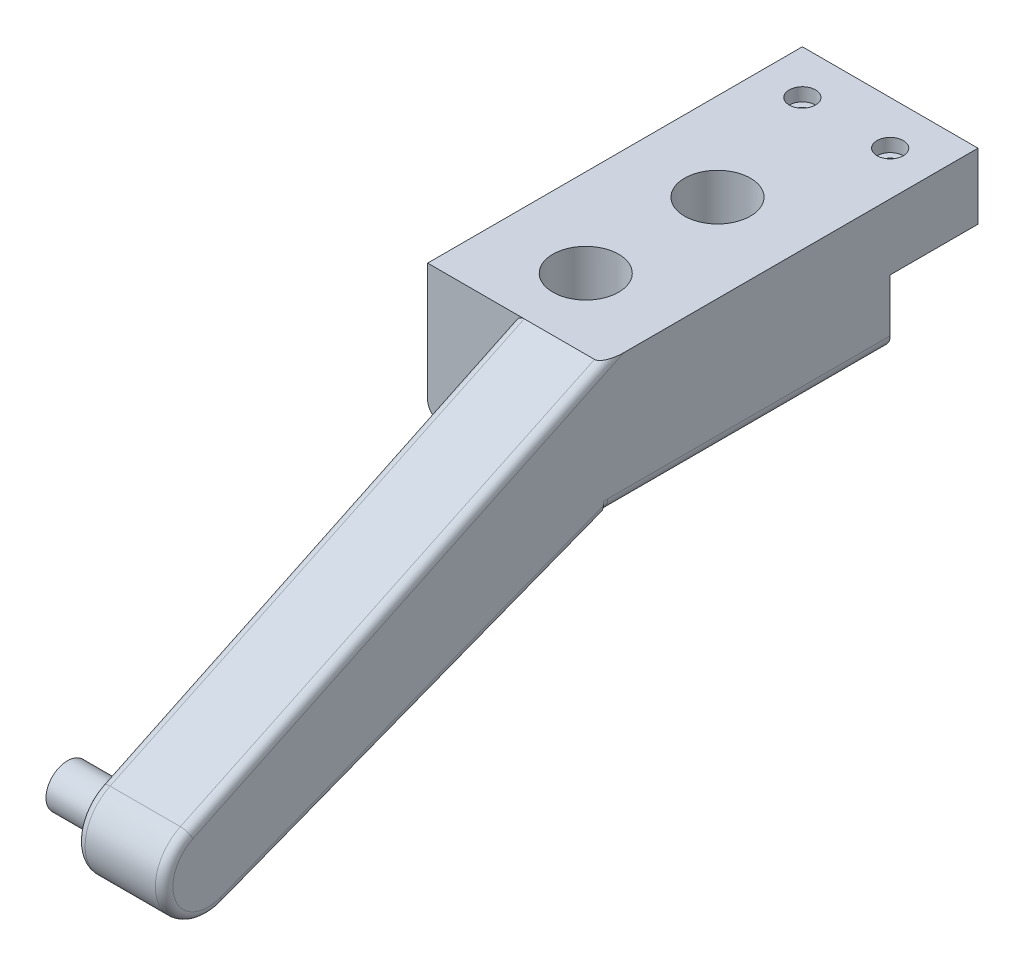
SolidWorks part; units mm, degrees
ref_plane "Front Plane" through (0, 0, 0) normal (0, 0, 1) x (1, 0, 0)
ref_plane "Top Plane" through (0, 0, 0) normal (0, 1, 0) x (1, 0, 0)
ref_plane "Right Plane" through (0, 0, 0) normal (1, 0, 0) x (0, 0, -1)
sketch "Sketch1" plane through (0, 0, 0) normal (0, 1, 0) x (1, 0, 0)
  line L1 (-20, 75) -> (20, 75)
  line L3 (-20, -75) -> (20, -75)
  line L4 (20, -75) -> (20, 75)
  line L5 (-20, -75) -> (-20, 75)
  circle A0 centre (0, -61.1649) radius 7.5
  circle A1 centre (0, -31.1649) radius 7.5
extrude "Boss-Extrude1" add sketch "Sketch1" against normal blind 30 contours L5 L1 L4 L3
sketch "Sketch3" plane through (0, 0, 0) normal (0, 1, 0) x (1, 0, 0)
  circle A0 centre (0, -60) radius 7.5
  circle A1 centre (0, -30) radius 7.5
extrude "Cut-Extrude1" cut sketch "Sketch3" against normal blind 30 contours A0 | A1
sketch "Sketch4" plane through (-20, 0, 0) normal (-1, 0, 0) x (0, 0, 1)
  line L1 (-75, -30) -> (-75, 0) construction
  line L2 (-75, -8) -> (0, -30)
  line L3 (75, -30) -> (-75, -30) construction
  line L4 (0, -30) -> (-75, -30)
  line L5 (-75, -30) -> (-75, -8)
extrude "Cut-Extrude2" cut sketch "Sketch4" against normal blind 49
sketch "Sketch6" plane through (0, 0, -75) normal (0, 0, -1) x (-1, 0, 0)
  line L1 (-20, 0) -> (20, 0)
  line L2 (-20, 0) -> (-20, -30)
  line L3 (-20, -30) -> (20, -30)
  line L4 (20, 0) -> (20, -30)
extrude "Boss-Extrude2" add sketch "Sketch6" along normal blind 50 and the other way blind 87
sketch "Sketch7" plane through (-20, 0, 0) normal (-1, 0, 0) x (0, 0, 1)
  line L1 (-125, -30) -> (-125, 0) construction
  line L2 (-125, -10) -> (-25, -30)
  line L3 (75, -30) -> (-125, -30) construction
  line L4 (-25, -30) -> (-125, -30)
  line L5 (-125, -30) -> (-125, -10)
extrude "Cut-Extrude3" cut sketch "Sketch7" against normal blind 50
sketch "Sketch8" plane through (0, 0, 75) normal (0, 0, 1) x (1, 0, 0)
  line L10 (20, -30) -> (6, -30)
  line L11 (-20, -30) -> (20, -30) construction
  line L12 (6, -30) -> (6, 0)
  line L13 (-20, 0) -> (20, 0) construction
  line L14 (6, 0) -> (20, 0)
  line L15 (20, 0) -> (20, -30)
  line L16 (-20, -30) -> (-6, -30)
  line L17 (-6, -30) -> (-6, 0)
  line L18 (-6, 0) -> (-20, 0)
  line L19 (-20, -30) -> (-20, 0) construction
  line L20 (-20, 0) -> (-20, -30)
extrude "Boss-Extrude4" add sketch "Sketch8" along normal blind 50
sketch "Sketch11" plane through (0, 0, 0) normal (0, 1, 0) x (1, 0, 0)
  line L0 (6, -75) -> (20, -75)
  line L1 (20, -125) -> (20, 125) construction
  line L2 (20, -75) -> (20, -125)
  line L3 (20, -125) -> (6, -125)
  line L4 (6, -125) -> (6, -75)
  line L5 (-6, -75) -> (-6, -125)
  line L6 (-6, -125) -> (-20, -125)
  line L7 (-20, -125) -> (-20, -75)
  line L8 (-20, -125) -> (-20, 125) construction
  line L9 (-20, -75) -> (-6, -75)
extrude "Cut-Extrude4" cut sketch "Sketch11" against normal blind 15
sketch "Sketch12" plane through (0, 0, 125) normal (0, 0, 1) x (1, 0, 0)
  line L1 (-20, -15) -> (-6, -15)
  line L2 (-20, -15) -> (-20, -30)
  line L3 (-20, -30) -> (-6, -30)
  line L4 (-6, -15) -> (-6, -30)
  line L5 (6, -15) -> (20, -15)
  line L6 (6, -15) -> (6, -30)
  line L7 (6, -30) -> (20, -30)
  line L8 (20, -15) -> (20, -30)
extrude "Boss-Extrude5" add sketch "Sketch12" along normal blind 10
sketch "Sketch13" plane through (-6, 0, 0) normal (1, 0, 0) x (0, 0, -1)
  circle A0 centre (-125, -22.5) radius 5
extrude "Boss-Extrude6" add sketch "Sketch13" along normal up to surface (12 mm away) contours A0 up to face at (6, -22.5, 105)
sketch "Sketch14" plane through (0, -30, 0) normal (0, -1, 0) x (1, 0, 0)
  circle A0 centre (0, 60) radius 7.5
  circle A1 centre (0, 60) radius 6
  circle A2 centre (0, 30) radius 6
  circle A3 centre (0, 30) radius 7.5
extrude "Boss-Extrude7" add sketch "Sketch14" against normal blind 5
sketch "Sketch15" plane through (20, 0, 0) normal (1, 0, 0) x (0, 0, -1)
  line L0 (125, 0) -> (105, 0)
  line L1 (-75, 0) -> (125, 0) construction
  circle A0 centre (52.5, 373.9316) radius 377.5991
extrude "Cut-Extrude5" cut sketch "Sketch15" against normal blind 50 contours A0
fillet "Fillet1" radius 3 2 edges at (20, -30, 55) (-20, -30, 55)
fillet "Fillet2" radius 3 8 edges at (-20, -18.5, -82.5) (-19.1213, -29.1213, -29.3934) (0, -30, -25) (19.1213, -29.1213, -29.3934) (-20, -5, -125) (20, -5, -125) (0, -10, -125) (20, -18.5, -82.5)
sketch "Sketch17" plane through (0, 0, 75) normal (0, 0, 1) x (1, 0, 0)
  line L0 (20, 0) -> (20, -30)
  line L1 (14.0365, -30) -> (20, -30)
  line L2 (6, -30) -> (17, -30) construction
  line L3 (20, 0) -> (-20, 0)
  line L4 (-20, 0) -> (-20, -30)
  line L5 (-20, -30) -> (14.0365, -30)
extrude "Boss-Extrude11" add sketch "Sketch17" along normal up to surface (60 mm away) up to face at (13.9243, -23.5243, 135)
sketch "Sketch23" plane through (0, 0, 135) normal (0, 0, 1) x (1, 0, 0)
  line L0 (-20, -15) -> (0, -15)
  line L1 (-20, 0) -> (-20, -30) construction
  line L3 (0, -30) -> (0, -15)
  line L4 (-20, -30) -> (20, -30) construction
  line L6 (-20, -30) -> (0, -30)
  line L7 (-20, -15) -> (-20, -30)
  line L9 (-20, -30) -> (20, -30)
  line L10 (-20, -30) -> (-20, 0)
  line L11 (-20, 0) -> (20, 0)
  line L12 (20, -30) -> (20, 0)
  line M1 (-20, 0) -> (-20, -30)
  line M2 (-20, -30) -> (20, -30)
  line M3 (20, -30) -> (20, 0)
  line M4 (20, 0) -> (-20, 0)
extrude "Cut-Extrude8" cut sketch "Sketch23" against normal up to surface (60 mm away) contours L3 L0 M2 M3 M4 M1 region at (3.3333, -12.5, 135) up to face at (19.2071, -29.2071, 75)
sketch "Sketch25" plane through (0, 0, 75) normal (0, 0, 1) x (1, 0, 0)
  line L0 (-20, -15) -> (-20, 0)
  line L1 (-20, 0) -> (0, 0)
  line L2 (-20, 0) -> (20, 0) construction
  line L3 (0, 0) -> (0, -15)
  line L4 (0, -15) -> (-20, -15)
extrude "Boss-Extrude13" add sketch "Sketch25" along normal up to surface (60 mm away) up to face at (-10, -22.5, 135)
sketch "Sketch26" plane through (0, 0, 0) normal (1, 0, 0) x (0, 0, -1)
  circle A0 centre (-125, -15) radius 5
extrude "Boss-Extrude14" add sketch "Sketch26" along normal up to surface (20 mm away) up to face at (20, -9.3154, -31.9576)
sketch "Sketch27" plane through (0, 0, 75) normal (0, 0, 1) x (1, 0, 0)
  line L1 (20, 0) -> (-20, 0)
  line L2 (20, 0) -> (20, -60)
  line L3 (20, -60) -> (-20, -60)
  line L4 (-20, 0) -> (-20, -60)
extrude "Boss-Extrude15" add sketch "Sketch27" along normal up to surface (60 mm away) up to face at (-10, -15, 135)
sketch "Sketch28" plane through (0, 0, 75) normal (0, 0, -1) x (-1, 0, 0)
  line L0 (20, -27) -> (20, -60) construction
  line L1 (-20, -60) -> (20, -60)
  line L2 (-20, -60) -> (-20, -30)
  line L3 (-20, -30) -> (20, -30)
  line L4 (20, -60) -> (20, -30)
extrude "Cut-Extrude9" cut sketch "Sketch28" against normal blind 1
sketch "Sketch29" plane through (0, 0, 135) normal (0, 0, 1) x (1, 0, 0)
  line L0 (20, 0) -> (-20, 0) construction
  line L1 (20, -60) -> (0, -60)
  line L2 (20, -60) -> (20, 0)
  line L3 (20, 0) -> (0, 0)
  line L4 (0, -60) -> (0, 0)
extrude "Cut-Extrude10" cut sketch "Sketch29" against normal up to surface (59 mm away) up to face at (0, -45, 76)
fillet "Fillet6" radius 3 1 edges at (-20, -30, 75.5)
fillet "Fillet7" radius 3 1 edges at (20, -30, 75.5)
sketch "Sketch30" plane through (0, 0, 135) normal (0, 0, 1) x (1, 0, 0)
  line L0 (-20, 0) -> (-20, -30)
  line L1 (-20, 0) -> (-20, -60) construction
  line L2 (-20, -15) -> (0, -15)
  line L3 (0, 0) -> (0, -60) construction
  line L4 (0, -15) -> (0, 0)
  line L5 (0, 0) -> (-20, 0)
  line M1 (0, -60) -> (0, 0)
  line M2 (0, 0) -> (-20, 0)
  line M3 (-20, 0) -> (-20, -60)
extrude "Cut-Extrude11" cut sketch "Sketch30" against normal up to surface (59 mm away) contours L2 M3 M1 M2 region at (-10, -7.5, 135) up to face at (11.5243, -17.5243, 76)
sketch "Sketch31" plane through (0, 0, 0) normal (1, 0, 0) x (0, 0, -1)
  line L0 (-129.7694, -41.2162) -> (-129.0122, -40.847)
  line L1 (-76, -15) -> (-76, -30)
  line L2 (-76, -30) -> (-118.7075, -57.7744)
  line L3 (-129.6113, -41.0081) -> (-129.7694, -41.2162)
  line L4 (-89.6197, -15) -> (-129.6113, -41.0081)
  line L5 (-76, -30) -> (-76, -60)
  line L6 (-76, -60) -> (-135, -60)
  line L7 (-135, -60) -> (-135, -15)
  line L8 (-135, -15) -> (-76, -15)
  line L9 (-96, -19.1494) -> (-129.6113, -41.0081) construction
  line L10 (-96, -15) -> (-96, -19.1494) construction
  circle A0 centre (-125.0122, -50.0122) radius 10
  line M9 (-76, -15) -> (-135, -15)
  line M10 (-135, -15) -> (-135, -60)
  line M11 (-135, -60) -> (-76, -60)
  line M12 (-76, -60) -> (-76, -30)
  dimension "D1" = 20
extrude "Cut-Extrude13" cut sketch "Sketch31" against normal blind 28 contours A0 M10 M11 | A0 L2 M11 M12 | A0 L3 L4 M9 M10 region at (0, -24.9817, 119.9741) region at (0, -57.7806, 132.7806) region at (0, -50.0084, 91.4032)
sketch "Sketch32" plane through (0, 0, 0) normal (1, 0, 0) x (0, 0, -1)
  line L0 (-76, -30) -> (-76, 0)
  line L1 (-76, 0) -> (-129.7694, -41.2162)
  line L2 (-129.7694, -41.2162) -> (-76, -30)
extrude "Boss-Extrude16" add sketch "Sketch32" against normal up to surface (20 mm away) up to face at (-20, -28.5466, 55.3206)
sketch "Sketch33" plane through (0, 0, 0) normal (1, 0, 0) x (0, 0, -1)
  circle A0 centre (-125.0122, -50.0122) radius 5
extrude "Boss-Extrude17" add sketch "Sketch33" along normal up to surface (20 mm away) contours A0 up to face at (20, -11.526, -18.3379)
ref_plane "Plane2" through (0, 10, 0) normal (0, 1, 0) x (1, 0, 0)
sketch "Sketch34" plane through (0, 0, 0) normal (1, 0, 0) x (0, 0, -1)
  line L0 (-129.6113, -41.0081) -> (-129.7694, -41.2162)
  line L1 (-129.6113, -41.0081) -> (-76, 0)
  line L2 (-76, 0) -> (-76, -30)
  line L3 (-76, -30) -> (-76, 0) construction
  line L4 (-76, -30) -> (-118.7075, -57.7744)
  arc A0 (-129.7694, -41.2162) -> (-118.7075, -57.7744) centre (-125.0122, -50.0122) ccw
extrude "Cut-Extrude15" cut sketch "Sketch34" against normal up to surface (20 mm away) up to face at (-20, -30.8448, 56.4126)
extrude "Cut-Extrude16" cut sketch "Sketch34<2>" along normal up to surface (20 mm away) up to face at (20, -11.526, -18.3379)
sketch "Sketch34<2>" plane through (0, 0, 0) normal (1, 0, 0) x (0, 0, -1) same geometry as "Sketch34"
extrude "Boss-Extrude19" add sketch "Sketch34<3>" along normal up to surface (20 mm away) up to face at (20, -11.526, -18.3379)
sketch "Sketch34<3>" plane through (0, 0, 0) normal (1, 0, 0) x (0, 0, -1) same geometry as "Sketch34"
sketch "Sketch38" plane through (0, 0, 0) normal (-1, 0, 0) x (0, 0, 1)
  circle A0 centre (125.0122, -50.0122) radius 5
sketch "Sketch39" plane through (0, 0, 0) normal (-1, 0, 0) x (0, 0, 1)
  line L0 (162.0273, -59.1835) -> (76, -78.9424)
  line L1 (169.997, -40.8408) -> (76, 0)
  line L2 (76, -30) -> (76, 0) construction
  line L3 (76, 0) -> (129.6113, -41.0081) construction
  line L4 (76, 0) -> (76, -30)
  line L6 (162.0273, -59.1835) -> (76, -30)
  line L7 (76, -78.9424) -> (76, -30)
  arc A0 (162.0273, -59.1835) -> (169.997, -40.8408) centre (166.0122, -50.0122) ccw
  line M6 (129.6113, -41.0081) -> (76, 0)
  line M8 (76, -30) -> (118.7075, -57.7744)
  arc M9 (118.7075, -57.7744) -> (129.7694, -41.2162) centre (125.0122, -50.0122) ccw
  line M10 (129.7694, -41.2162) -> (129.6113, -41.0081)
extrude "Cut-Extrude17" cut sketch "Sketch39" against normal blind 23 contours L7 L0 L6 M9 M8 | L6 M9 M8 region at (0, -58.461, 102.3812) region at (0, -47.5284, 112.7515)
extrude "Boss-Extrude21" add sketch "Sketch39<3>" against normal blind 20 contours L6 A0 L1 M6 M10 M9 region at (0, -36.3816, 138.4753)
sketch "Sketch39<3>" plane through (0, 0, 0) normal (-1, 0, 0) x (0, 0, 1) same geometry as "Sketch39"
sketch "Sketch40" plane through (0, -4.0074, 0) normal (-1, 0, 0) x (0, 0, 1)
  circle A0 centre (166.0122, -50.0122) radius 4.5
extrude "Boss-Extrude22" add sketch "Sketch40" along normal up to surface (12 mm away)
ref_plane "Plane5" through (0, 0, 0) normal (-1, 0, 0) x (0, 0, 1)
sketch "Sketch42" plane through (0, 0, 0) normal (-1, 0, 0) x (0, 0, 1)
  line L0 (166.0122, -54.0196) -> (166.0122, -54.0122)
  line L1 (170.3172, -44.9863) -> (76, 0)
  line L2 (76, 0) -> (76, -30)
  line L3 (162.4124, -63.3418) -> (76, -30)
  line L4 (175.8593, -55.7544) -> (179.2704, -36.4741)
  line L5 (179.2704, -36.4741) -> (76, 0)
  circle A0 centre (166.0122, -54.0122) radius 10
extrude "Cut-Extrude18" cut sketch "Sketch42" against normal blind 20 contours A0 L4 L5 L1 region at (0, -28.5967, 144.6768)
extrude "Boss-Extrude23" add sketch "Sketch42<4>" against normal blind 20 contours A0 L1 L2 L3 | A0 region at (0, -31.8969, 115.5317) region at (0, -48.8269, 174.2302)
sketch "Sketch42<4>" plane through (0, 0, 0) normal (-1, 0, 0) x (0, 0, 1) same geometry as "Sketch42"
sketch "Sketch43" plane through (0, 0, 0) normal (-1, 0, 0) x (0, 0, 1)
  circle A0 centre (166.0122, -54.0196) radius 5.5
extrude "Boss-Extrude24" add sketch "Sketch43" along normal blind 2
fillet "Fillet8" radius 2 6 edges at (20, -46.6709, 119.2062) (20, -57.9675, 175.1967) (0, -46.6709, 119.2062) (0, -57.9675, 175.1967) (20, -22.4932, 123.1586) (0, -22.4932, 123.1586)
sketch "Sketch44" plane through (20, 0, 0) normal (1, 0, 0) x (0, 0, -1)
  line L0 (0, 0) -> (105, 0)
  line L1 (105, 0) -> (105, -4.5055)
  line L2 (105, -4.5055) -> (0, -4.5055)
  line L3 (0, -4.5055) -> (0, 0)
extrude "Boss-Extrude25" add sketch "Sketch44" against normal up to surface (40 mm away) up to face at (-20, -11.526, -18.3379)
sketch "Sketch46" plane through (20, 0, 0) normal (1, 0, 0) x (0, 0, -1)
  line L0 (-71.3543, 0) -> (122, 0) construction
  line L1 (25.3229, 0) -> (-14.6771, 0)
  line L2 (25.3229, 0) -> (25.3229, -6)
  line L3 (25.3229, -27) -> (-14.6771, -27)
  line L4 (-14.6771, 0) -> (-14.6771, -27)
  line L5 (-75, -27) -> (24.7029, -27) construction
  line L6 (63.8734, -19.1659) -> (62.5127, -12.362)
  line L7 (24.7029, -27) -> (122, -7.5406) construction
  line L8 (19.3229, -6) -> (-8.6771, -6)
  line L9 (-8.6771, -6) -> (-8.6771, -21)
  line L10 (19.3229, -21) -> (-8.6771, -21)
  line L12 (19.3229, -21) -> (94.3229, -6)
  line L13 (19.3229, -6) -> (103.4664, -6)
  line L14 (25.3229, -19.8) -> (25.3229, -27)
  line L15 (19.3229, -6) -> (19.3229, -21) construction
  line L16 (25.3229, 0) -> (25.3229, -27) construction
  dimension "D1" = 6
extrude "Cut-Extrude20" cut sketch "Sketch46" against normal blind 59 and the other way through all contours L13 L8 L9 L10 L12 region at (20, -12.0687, -27.6511)
fillet "Fillet10" radius 2 1 edges at (0, -6, -94.3229)
sketch "Sketch47" plane through (-12, 0, 0) normal (-1, 0, 0) x (0, 0, 1)
  circle A0 centre (166.0122, -54.0196) radius 5
extrude "Boss-Extrude26" add sketch "Sketch47" against normal up to surface (10 mm away) up to face at (-2, -54.0196, 170.5122)
sketch "Sketch48" plane through (0, 0, 8.6771) normal (0, 0, -1) x (-1, 0, 0)
  line L0 (-20, -21) -> (20, -21)
  line L1 (-20, -21) -> (-20, -6)
  line L2 (20, -21) -> (20, -6)
  line L3 (-20, -6) -> (20, -6)
extrude "Boss-Extrude28" add sketch "Sketch48" along normal blind 28
sketch "Sketch49" plane through (20, 0, 0) normal (1, 0, 0) x (0, 0, -1)
  line L0 (19.3229, -6) -> (19.3229, 0)
  line L7 (-71.3543, 0) -> (122, 0) construction
  line L8 (19.3229, -6) -> (19.3229, -30)
  line L9 (19.3229, -30) -> (-20.6771, -30)
  line L10 (-20.6771, -30) -> (-20.6771, 0)
  line L11 (-20.6771, 0) -> (19.3229, 0)
  line L12 (-20.6771, -30) -> (-10.6771, -30)
  line L13 (-10.6771, -30) -> (-10.6771, -15)
  line L14 (-10.6771, -15) -> (9.3229, -15)
  line L15 (9.3229, -15) -> (9.3229, 0)
  line M5 (19.3229, -21) -> (19.3229, -6)
  line M9 (122, 0) -> (-71.3543, 0)
  line M15 (-75, -27) -> (24.7029, -27)
sketch "Sketch50" plane through (0, 0, 0) normal (0, 1, 0) x (1, 0, 0)
  line L0 (20, 9.3229) -> (-20, 9.3229)
  line L1 (-20, -76) -> (-20, 122) construction
  line L2 (-20, 9.3229) -> (-20, -0.6771)
  line L3 (-20, -0.6771) -> (-10, -0.6771)
  line L4 (-10, -0.6771) -> (10, -0.6771)
  circle A0 centre (10, -0.6771) radius 1.5
  circle A1 centre (-10, -0.6771) radius 1.5
extrude "Cut-Extrude21" cut sketch "Sketch49" against normal blind 49 contours L15 L14 L13 L8 L0 M15 M5 M9 | L13 L9 L8 M15 region at (20, -17.0294, -7.264) region at (20, -28.5, -4.3229)
sketch "Sketch51" plane through (0, 0, -19.3229) normal (0, 0, 1) x (1, 0, 0)
  line L1 (24.2973, -37.591) -> (-28.6622, -37.591)
  line L2 (24.2973, -37.591) -> (24.2973, 2.6321)
  line L3 (24.2973, 2.6321) -> (-28.6622, 2.6321)
  line L4 (-28.6622, -37.591) -> (-28.6622, 2.6321)
extrude "Cut-Extrude22" cut sketch "Sketch51" against normal blind 136
extrude "Cut-Extrude23" cut sketch "Sketch50" against normal blind 136 contours A0 | L3 A1 L4 | L4 A1 L3 region at (-10, 0, 0.0405) region at (10, 0, -0.7804) region at (-10, 0, 1.3138)
sketch "Sketch52" plane through (0, 0, 0) normal (0, 1, 0) x (1, 0, 0)
  circle A0 centre (10, -0.6771) radius 3
  circle A1 centre (-10, -0.6771) radius 3
  circle A2 centre (10, -0.6771) radius 1.5
  circle A3 centre (-10, -0.6771) radius 1.5
extrude "Cut-Extrude24" cut sketch "Sketch52" against normal blind 3
sketch "Sketch53" plane through (-2, 0, 0) normal (-1, 0, 0) x (0, 0, 1)
  circle A0 centre (166.0122, -54.0196) radius 4.9
  circle A1 centre (166.0122, -54.0196) radius 6.0968
extrude "Cut-Extrude25" cut sketch "Sketch53" along normal blind 16
